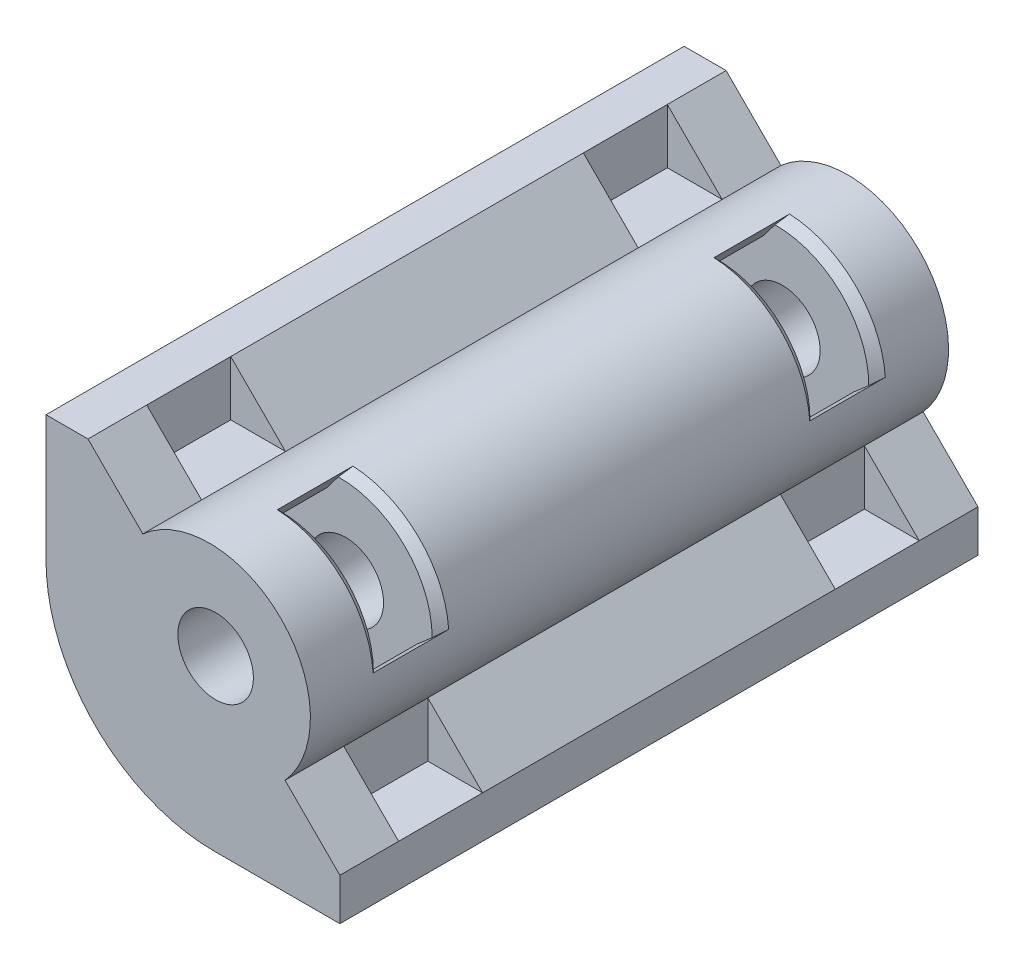
SolidWorks part; units mm, degrees
ref_plane "Front Plane" through (0, 0, 0) normal (0, 0, 1) x (1, 0, 0)
ref_plane "Top Plane" through (0, 0, 0) normal (0, 1, 0) x (1, 0, 0)
ref_plane "Right Plane" through (0, 0, 0) normal (1, 0, 0) x (0, 0, -1)
sketch "Sketch1" plane through (0, 0, 0) normal (0, 0, 1) x (1, 0, 0)
  line L0 (17.5, 2.5) -> (14.235, 5.765)
  line L1 (10, 0) -> (17.5, 0)
  line L2 (0, 10) -> (0, 17.5)
  line L5 (2.5, 17.5) -> (0, 17.5)
  line L6 (17.5, 2.5) -> (17.5, 0)
  line L9 (5.765, 14.235) -> (2.5, 17.5)
  arc A0 (10, 0) -> (0, 10) centre (10, 10) cw
  arc A1 (14.235, 5.765) -> (5.765, 14.235) centre (9.7458, 9.7458) ccw
  circle A2 centre (10.1, 10.1) radius 2.25
  point P5 (2.5, 2.5)
  point P10 (0, 0)
  dimension "D3" = 10
  dimension "D2" = 6
  dimension "D4" = 4.5
extrude "corner" add sketch "Sketch1" along normal mid plane 38
sketch "Sketch4" plane through (0, 0, 19) normal (0, 0, 1) x (1, 0, 0)
  line L0 (8.9643, 14.3383) -> (12.2893, 18.7168)
  line L1 (13.2027, 13.2027) -> (8.9643, 14.3383) construction
  line L2 (8.9643, 14.3383) -> (5.8617, 11.2357)
  line L3 (5.8617, 11.2357) -> (6.9973, 6.9973)
  line L4 (6.9973, 6.9973) -> (11.2357, 5.8617)
  line L5 (11.2357, 5.8617) -> (14.3383, 8.9643)
  line L6 (14.3383, 8.9643) -> (13.2027, 13.2027) construction
  line L7 (12.2893, 18.7168) -> (18.5446, 12.6018)
  line L8 (18.5446, 12.6018) -> (14.3383, 8.9643)
  circle A0 centre (10.1, 10.1) radius 3.8 construction
  circle A1 centre (10.1, 10.1) radius 2.1 construction
  dimension "D1" = 7.6
extrude "nut" cut sketch "Sketch4" against normal mid plane 3.5 from offset 6 offset against normal yes
chamfer "Chamfer1" distance 0.5 angle 45 2 edges at (13.9383, 14.0379, 14.75) (13.9383, 14.0379, 11.25)
sketch "Sketch6" plane through (0, 0, 19) normal (0, 0, 1) x (1, 0, 0)
  line L0 (2.5, 17.5) -> (2.5, 14.235)
  line L1 (2.5, 14.235) -> (5.765, 14.235)
  line L2 (5.765, 14.235) -> (2.5, 17.5)
  line L3 (14.235, 5.765) -> (14.235, 2.5)
  line L4 (14.235, 2.5) -> (17.5, 2.5)
  line L5 (17.5, 2.5) -> (14.235, 5.765)
extrude "Cut-Extrude1" cut sketch "Sketch6" against normal mid plane 5 from offset 6 offset against normal yes
mirror "Mirror1" about plane through (0, 0, 0) normal (0, 0, 1) of "Cut-Extrude1", "Chamfer1", "nut"
